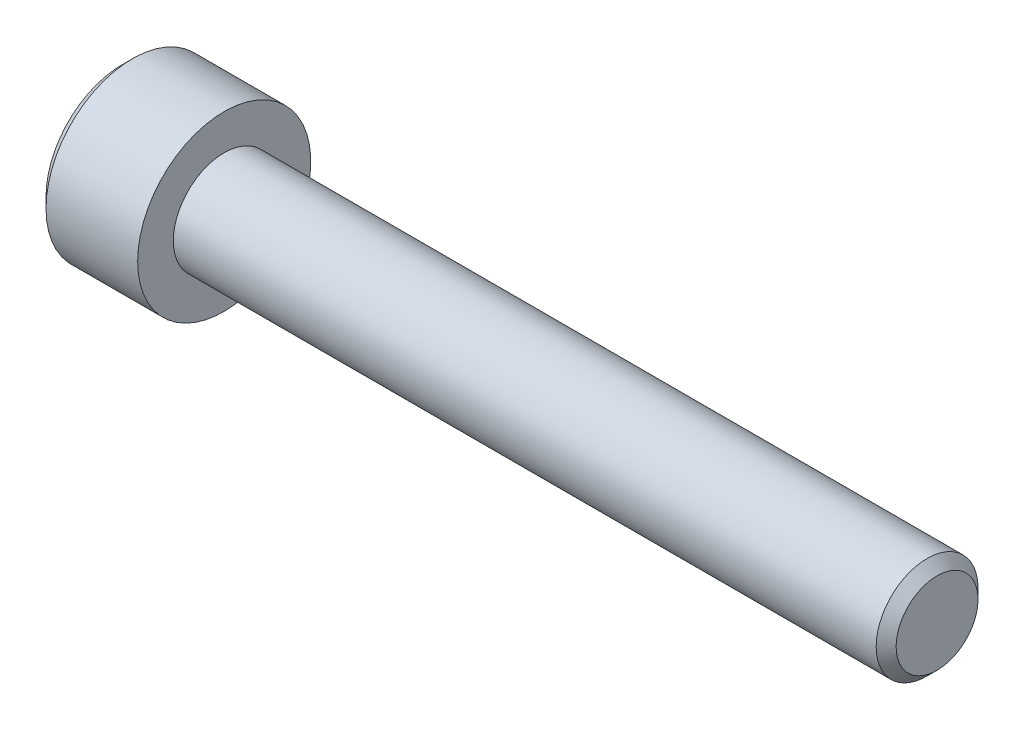
SolidWorks part; units mm, degrees
material "SUS304相当"
ref_plane "Front Plane" through (0, 0, 0) normal (0, 0, 1) x (1, 0, 0)
ref_plane "Top Plane" through (0, 0, 0) normal (0, 1, 0) x (1, 0, 0)
ref_plane "Right Plane" through (0, 0, 0) normal (1, 0, 0) x (0, 0, -1)
ref_plane "Plane1" through (1, 0, 0) normal (1, 0, 0) x (0, 0, -1)
ref_axis "Axis_X" through (-7, 0, 0) along (1, 0, 0)
ref_axis "Axis_Y" through (0, 4.675, 0) along (0, -1, 0)
ref_axis "Axis_Z" through (0, 0, -4.675) along (0, 0, 1)
sketch "Sketch1" plane through (0, 0, 0) normal (0, 0, 1) x (1, 0, 0)
  line L0 (-5, 0) -> (35, 0)
  line L1 (35, 0) -> (35, -2.0095)
  line L2 (35, -2.0095) -> (34.5095, -2.5)
  line L3 (34.5095, -2.5) -> (0, -2.5)
  line L4 (0, -2.5) -> (0, -4.25)
  line L5 (0, -4.25) -> (-4.5, -4.25)
  line L6 (-4.5, -4.25) -> (-5, -3.75)
  line L7 (-5, -3.75) -> (-5, 0)
  line L8 (0, 0) -> (-5, 0) construction
  line L9 (35, 2.0095) -> (34.5095, 2.5) construction
  line L10 (-5, 3.75) -> (-4.5, 4.25) construction
  point P16 (34.2, -2.5)
  dimension "A" = 8.5
  dimension "E" = 5
  dimension "MSM_1" = 4.019
  dimension "MSM_2" = 45
  dimension "MSM_3" = 0.5
  dimension "L" = 35
  dimension "Pitch_1" = 0.8
revolve "Revolve1" add sketch "Sketch1" angle 360 about axis through (-7, 0, 0) along (1, 0, 0)
cosmetic thread "Thread1" [suppressed]
cosmetic thread "Thread2"
sketch "Sketch2" plane through (-5, 0, 0) normal (-1, 0, 0) x (0, 0, 1)
  line L1 (0, 2.3094) -> (-2, 1.1547)
  line L2 (-2, 1.1547) -> (-2, -1.1547)
  line L3 (-2, -1.1547) -> (0, -2.3094)
  line L4 (0, -2.3094) -> (2, -1.1547)
  line L5 (2, -1.1547) -> (2, 1.1547)
  line L6 (2, 1.1547) -> (0, 2.3094)
  circle A0 centre (0, 0) radius 2 construction
  dimension "B" = 4
extrude "Cut-Extrude1" cut sketch "Sketch2" against normal blind 2.5
ref_plane "Dim. B_s" through (35, 0, 0) normal (1, 0, 0) x (0, 0, -1)
sketch "Sketch3" plane through (0, 0, 0) normal (0, 0, 1) x (1, 0, 0)
  line L0 (0, 0) -> (35, 0) construction
  line L1 (35, -1.3128) -> (35, 1.3128) construction
  line L3 (34.99, 2.5) -> (35, 2.5)
  line L5 (34.99, 2.5) -> (34.99, 2.49)
  line L6 (34.99, 2.49) -> (35, 2.49)
  line L7 (35, 2.5) -> (35, 2.49)
  line L8 (32, 2.5) -> (32.01, 2.5)
  line L9 (32, 2.5) -> (32, 2.49)
  line L10 (32, 2.49) -> (32.01, 2.49)
  line L11 (32.01, 2.5) -> (32.01, 2.49)
  dimension "MSM_5" = 0.01
  dimension "A_s" = 3
revolve "Cut-Revolve1" [suppressed] cut sketch "Sketch3" angle 360 about L0
equation "\"Factor\"= 1.082532"
equation "\"ATD_1\"= 4.134"
equation "\"L_s\"= 10"
equation "\"L_s\"= IIF ( ( \"M\" = 12 and \"L\" > 50 ) , 36 , IIF ( ( \"M\" = 10 and \"L\" > 40 ) , 32 , IIF ( ( \"M\" = 8 and \"L\" > 35 ) , 28 , IIF ( ( \"M\" = 6 and \"L\" > 30 ) , 24 , IIF ( ( \"M\" = 5 and \"L\" > 25 ) , 22 , IIF ( ( \"M\" = 4 and \"L\" > 25 ) , 20 , IIF ( ( \"M\" = 3 and \"L\" > 20 ) , 18 , \"L\" ) ) ) ) ) ) )"
equation "\"A\"= IIF ( \"M\" = 12 , 18 , IIF ( \"M\" = 10 , 16 , IIF ( \"M\" = 8 , 13 , IIF ( \"M\" = 6 , 10 , IIF ( \"M\" = 5 , 8.5 , IIF ( \"M\" = 4 , 7 , IIF ( \"M\" = 3 , 5.5 , IIF ( \"M\" = 2.6 or \"M\" = 2.5 , 4.5 , 3.8 ) ) ) ) ) ) ) )"
equation "\"E\"= \"M\""
equation "\"B\"= IIF ( \"M\" = 12 , 10 , IIF ( \"M\" = 10 , 8 , IIF ( \"M\" = 8 , 6 , IIF ( \"M\" = 6 , 5 , IIF ( \"M\" = 5 , 4 , IIF ( \"M\" = 4 , 3 , IIF ( \"M\" = 3 , 2.5 , IIF ( \"M\" = 2.6 or \"M\" = 2.5 , 2 , 1.5 ) ) ) ) ) ) ) )"
equation "\"MSM_4\"= \"M\" * 0.5"
equation "\"MSM_1\"= IIF ( \"M\" = 12 , 9.853 , IIF ( \"M\" = 10 , 8.16 , IIF ( \"M\" = 8 , 6.466 , IIF ( \"M\" = 6 , 4.773 , IIF ( \"M\" = 5 , 4.019 , IIF ( \"M\" = 4 , 3.141 , IIF ( \"M\" = 3 , 2.387 , IIF ( \"M\" = 2.6 , 2.048 , IIF ( \"M\" = 2.5 , 1.948 , 1.509 ) ) ) ) ) ) ) ) )"
equation "\"MSM_2\"= 45"
equation "\"MSM_3\"= IIF ( \"M\" = 2.6 , 0.26 , \"E\" * 0.1 )"
equation "\"Thread1\" = IIF ( ( ( \"M\" = 12 ) and ( \"L\" > 50 ) ) or ( ( \"M\" = 10 ) and ( \"L\" > 40 ) ) or ( ( \"M\" = 8 ) and ( \"L\" > 35 ) ) or ( ( \"M\" = 6 ) and ( \"L\" > 30 ) ) or ( ( \"M\" = 5 ) and ( \"L\" > 25 ) ) or ( ( \"M\" = 4 ) and ( \"L\" > 25 ) ) or ( \"M\" = 3 ) and ( \"L\" > 2 ) , \"suppressed\" , \"unsuppressed\" )"
equation "\"Thread2\" = IIF ( ( ( \"M\" = 12 ) and ( \"L\" > 50 ) ) or ( ( \"M\" = 10 ) and ( \"L\" > 40 ) ) or ( ( \"M\" = 8 ) and ( \"L\" > 35 ) ) or ( ( \"M\" = 6 ) and ( \"L\" > 30 ) ) or ( ( \"M\" = 5 ) and ( \"L\" > 25 ) ) or ( ( \"M\" = 4 ) and ( \"L\" > 25 ) ) or ( \"M\" = 3 ) and ( \"L\" > 2 ) , \"unsuppressed\" , \"suppressed\" )"
equation "\"MSM_5\"= 0.01"
equation "\"Cut-Revolve1\"= IIF ( \"TYP\" = 2 , \"unsuppressed\" , \"suppressed\" )"
equation "\"Pitch_1\"= IIF ( \"M\" = 12 , 1.75 , IIF ( \"M\" = 10 , 1.5 , IIF ( \"M\" = 8 , 1.25 , IIF ( \"M\" = 6 , 1 , IIF ( \"M\" = 5 , 0.8 , IIF ( \"M\" = 4 , 0.7 , IIF ( \"M\" = 3 , 0.5 , IIF ( \"M\" = 2.6 or \"M\" = 2.5 , 0.45 , 0.4 ) ) ) ) ) ) ) )"
equation "\"ATD_2\"= round ( \"M\" - \"Factor\" * \"Pitch_1\" , 3 )"
